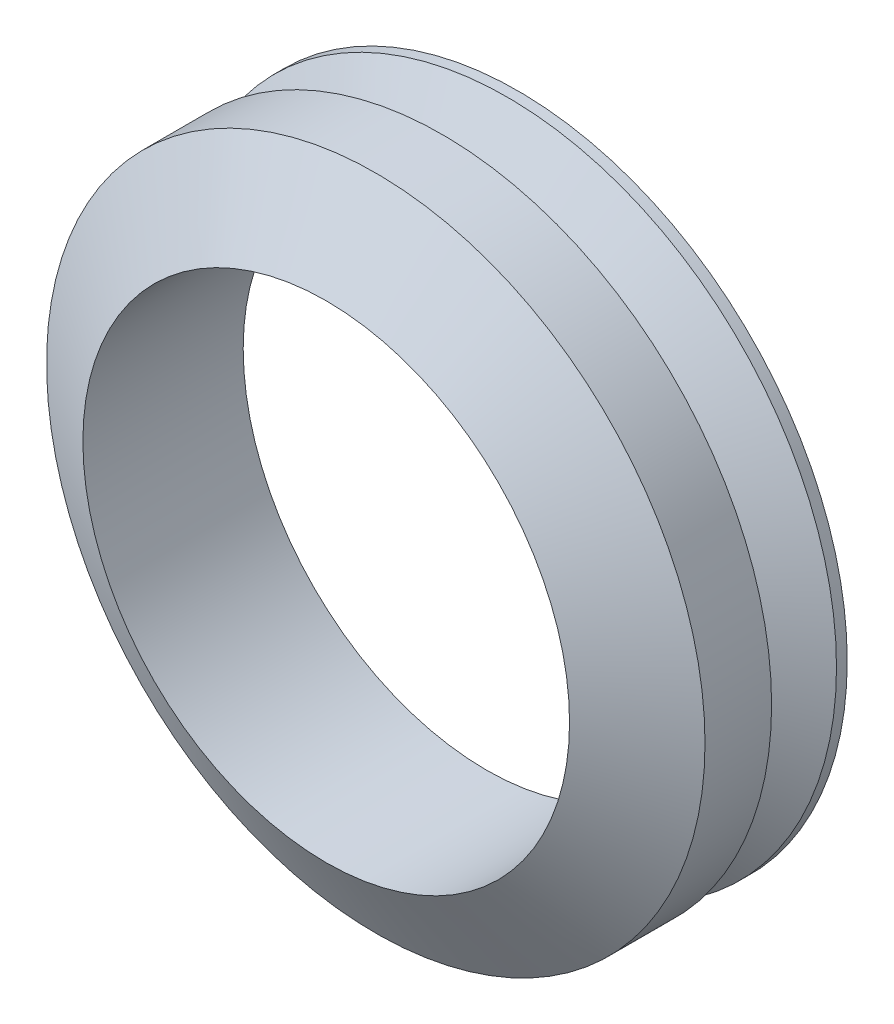
SolidWorks part; units mm, degrees
ref_plane "Plan1" through (0, 0, 0) normal (0, 0, 1) x (1, 0, 0)
ref_plane "Plan2" through (0, 0, 0) normal (0, 1, 0) x (1, 0, 0)
ref_plane "Plan3" through (0, 0, 0) normal (1, 0, 0) x (0, 0, -1)
sketch "Esquisse1" plane through (0, 0, 0) normal (1, 0, 0) x (0, 0, -1)
  line L0 (0, 0) -> (6.7, 0) construction
  line L1 (0, 8.5) -> (5.6, 8.5)
  line L2 (0, 8.5) -> (1.7321, 11.5)
  line L3 (1.7321, 11.5) -> (4.0582, 11.5)
  line L4 (4.0582, 11.5) -> (4.9317, 9.1)
  line L5 (5.6, 8.5) -> (6.7, 11.5)
  line L6 (6.325, 11.5) -> (6.7, 11.5)
  line L7 (6.325, 11.5) -> (4.9317, 9.1)
  dimension "D3" = 60
  dimension "dn" = 8.5
  dimension "c" = 3
  dimension "D4" = 70
  dimension "b" = 6.7
  dimension "D7" = 0.6
  dimension "A" = 5.6
  dimension "D8" = 10
  dimension "D9" = 0.375
revolve "Base-Révolution" add sketch "Esquisse1" angle 360 about L0
ref_axis "Axe1" through (0, 0, -50) along (0, 0, 1)
equation "\"D7@Esquisse1\"=\"c@Esquisse1\"/5"
equation "\"D9@Esquisse1\"=\"c@Esquisse1\"/8"
